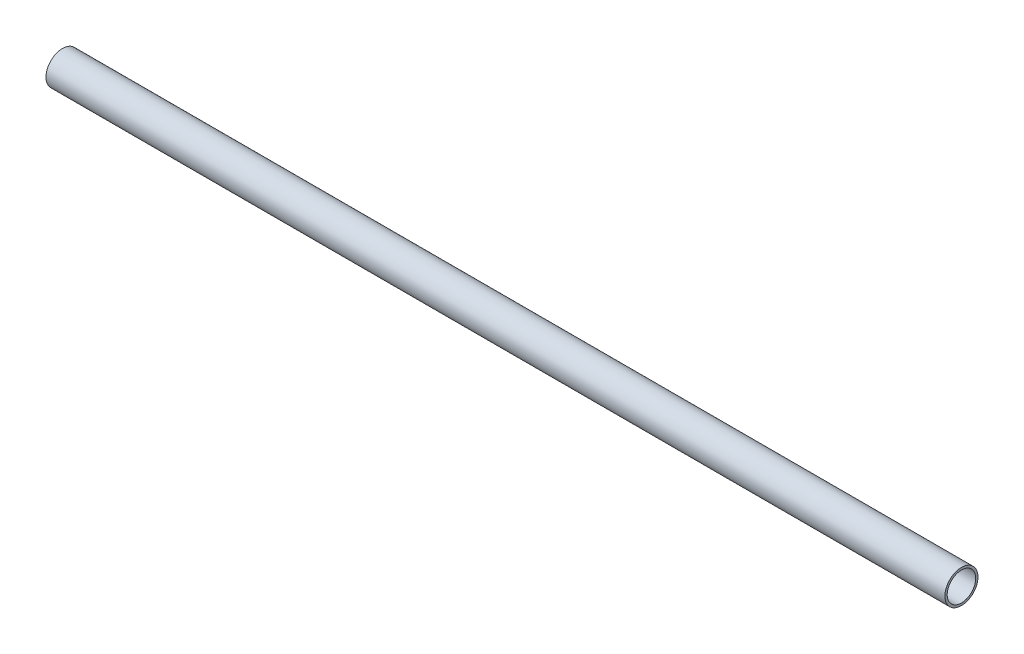
SolidWorks part; units mm, degrees
ref_plane "Front Plane" through (0, 0, 0) normal (0, 0, 1) x (1, 0, 0)
ref_plane "Top Plane" through (0, 0, 0) normal (0, 1, 0) x (1, 0, 0)
ref_plane "Right Plane" through (0, 0, 0) normal (1, 0, 0) x (0, 0, -1)
ref_axis "Axis1" through (-2, 0, 0) along (1, 0, 0)
sketch "Sketch1" plane through (0, 0, 0) normal (1, 0, 0) x (0, 0, -1)
  circle A0 centre (0, 0) radius 0.635
  circle A1 centre (0, 0) radius 0.7366
  dimension "D1" = 1.4732
  dimension "D2" = 1.27
extrude "Boss-Extrude1" add sketch "Sketch1" along normal blind 40
equation "\"Do\"=8.5mm"
equation "\"Lo\"=10"
equation "\"screw_diam\"= 3.5mm"
equation "\"wheel_Do\"=12.5mm"
equation "\"wheel_thickness\"=4mm"
equation "\"Collet_diameter\"=4.3"
equation "\"clearance\"= 0.5mm"
equation "\"handle_body_width\"= 10mm"
equation "\"finger_diameter\"=35"
equation "\"collet_lid_diameter\"=10"
equation "\"screw_cap_diam\"=5.15"
equation "\"handle_thickness\"=12.5mm"
equation "\"post_hole_diam\"=2"
equation "\"roll_rod_diam\"= 6.5 "
equation "\"roll_rod_length\"=6.6"
equation "\"disc_diam\"=5"
equation "\"disc_width\"=1.5"
equation "\"arm_width\"=5"
equation "\"arm_thickness\"=4.5"
equation "\"wheel_total_diam\"=30"
equation "\"spring_diam\"=4.1"
equation "\"collet_length\"= 18.75mm"
equation "\"tip_length\"= 40mm"
equation "\"D1@Boss-Extrude1\"=\"tip_length\""
